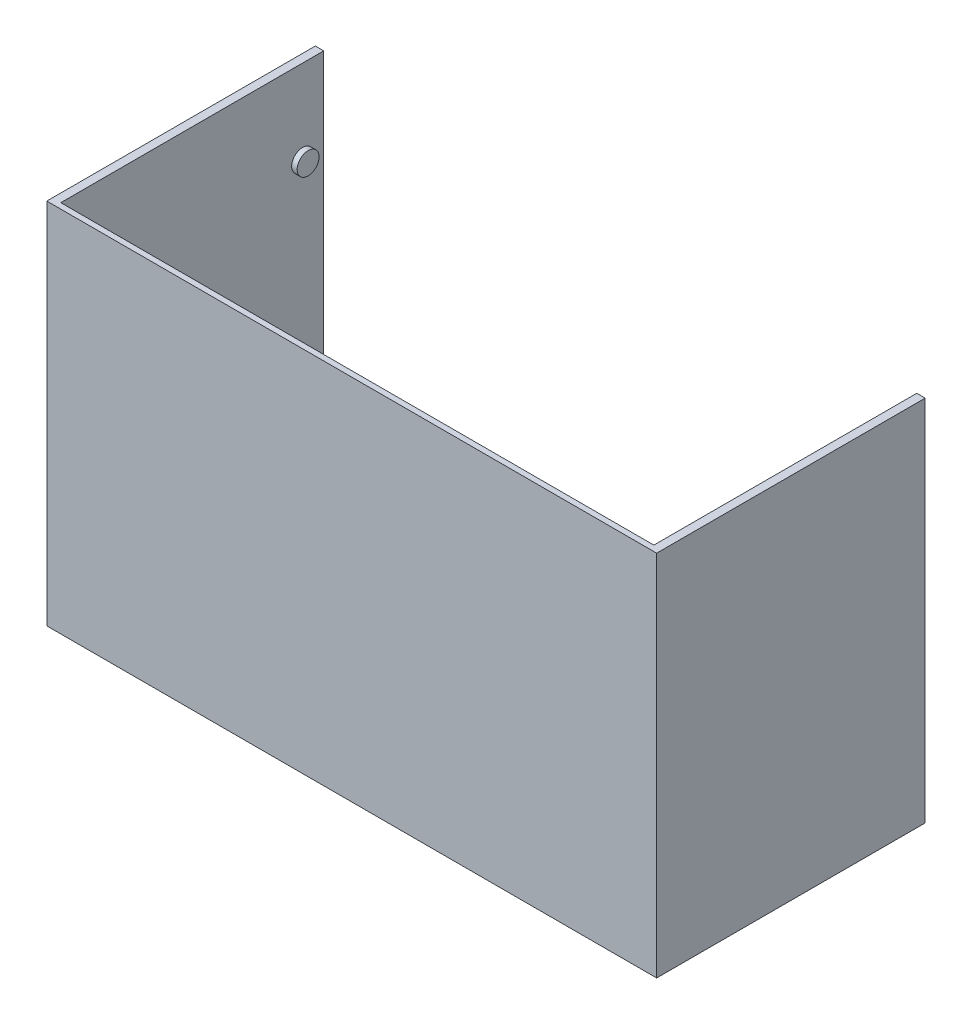
SolidWorks part; units mm, degrees
material "ABS PC"
ref_plane "Front Plane" through (0, 0, 0) normal (0, 0, 1) x (1, 0, 0)
ref_plane "Top Plane" through (0, 0, 0) normal (0, 1, 0) x (1, 0, 0)
ref_plane "Right Plane" through (0, 0, 0) normal (1, 0, 0) x (0, 0, -1)
sketch "Sketch1" plane through (0, 0, 0) normal (0, 0, 1) x (1, 0, 0)
  line L1 (-346.075, 208.788) -> (346.075, 208.788)
  line L2 (-346.075, 208.788) -> (-346.075, -208.788)
  line L3 (-346.075, -208.788) -> (346.075, -208.788)
  line L4 (346.075, 208.788) -> (346.075, -208.788)
  line L5 (-346.075, 208.788) -> (346.075, -208.788) construction
  line L6 (-346.075, -208.788) -> (346.075, 208.788) construction
  point P0 (0, 0)
  dimension "D1" = 417.576
  dimension "D2" = 692.15
extrude "Boss-Extrude1" add sketch "Sketch1" along normal blind 304.8
sketch "Sketch2" plane through (0, 0, 0) normal (0, 0, -1) x (-1, 0, 0)
  line L0 (346.075, -208.788) -> (-346.075, -208.788) construction
  line L1 (-336.55, 208.788) -> (336.55, 208.788)
  line L2 (-336.55, 208.788) -> (-336.55, -208.788)
  line L3 (-336.55, -208.788) -> (336.55, -208.788)
  line L4 (336.55, 208.788) -> (336.55, -208.788)
  line L5 (-336.55, 208.788) -> (336.55, -208.788) construction
  line L6 (-336.55, -208.788) -> (336.55, 208.788) construction
  point P0 (0, 0)
  dimension "D1" = 673.1
extrude "Cut-Extrude1" cut sketch "Sketch2" against normal blind 298.45
sketch "Sketch3" plane through (-346.075, 0, 0) normal (-1, 0, 0) x (0, 0, 1)
  circle A0 centre (23.9788, 113.4382) radius 12.446
  dimension "D1" = 24.892
extrude "Boss-Extrude2" add sketch "Sketch3" against normal blind 15.748 contours A0
